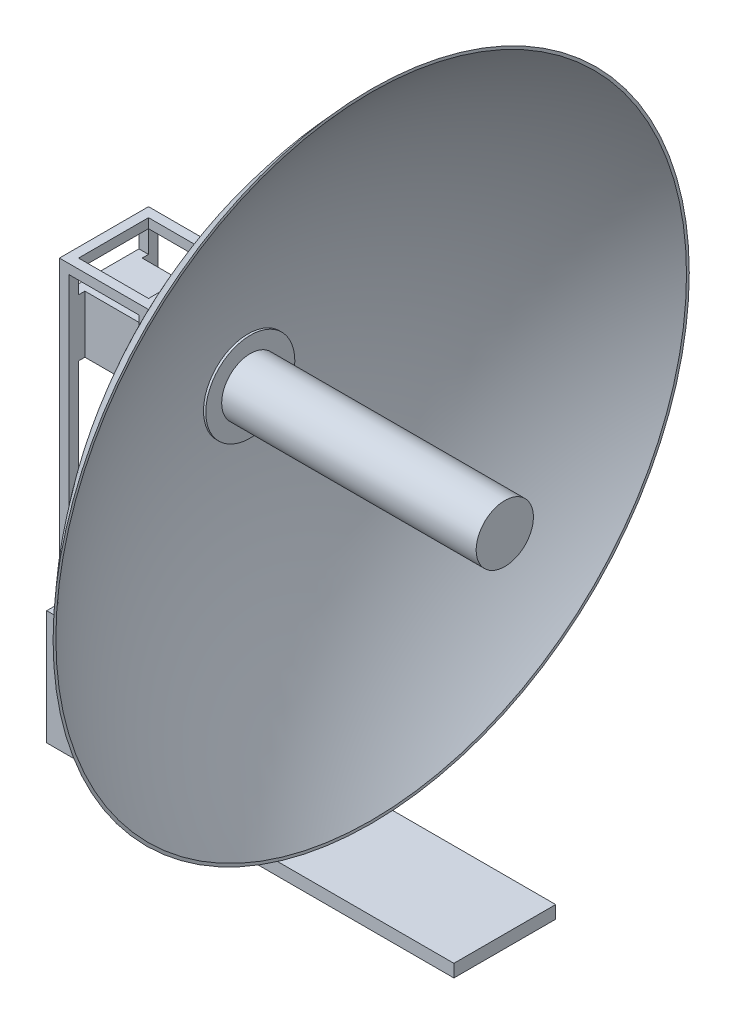
SolidWorks part; units mm, degrees
ref_plane "Front Plane" through (0, 0, 0) normal (0, 0, 1) x (1, 0, 0)
ref_plane "Top Plane" through (0, 0, 0) normal (0, 1, 0) x (1, 0, 0)
ref_plane "Right Plane" through (0, 0, 0) normal (1, 0, 0) x (0, 0, -1)
sketch "Sketch1" plane through (0, 0, 0) normal (0, 1, 0) x (1, 0, 0)
  line L1 (0, 0) -> (640, 0)
  line L2 (0, 0) -> (0, 160)
  line L3 (0, 160) -> (640, 160)
  line L4 (640, 0) -> (640, 160)
  dimension "D1" = 160
  dimension "D2" = 640
extrude "Boss-Extrude1" add sketch "Sketch1" along normal blind 180
sketch "Sketch2" plane through (640, 0, 0) normal (1, 0, 0) x (0, 0, -1)
  line L0 (160, 180) -> (160, 0) construction
  line L1 (0, 180) -> (160, 180)
  line L2 (0, 180) -> (0, 20)
  line L3 (0, 20) -> (160, 20)
  line L4 (160, 180) -> (160, 20)
  dimension "D1" = 160
extrude "Cut-Extrude1" cut sketch "Sketch2" against normal blind 480
sketch "Sketch3" plane through (160, 0, 0) normal (1, 0, 0) x (0, 0, -1)
  line L0 (0, 100) -> (160, 100) construction
  line L1 (0, 180) -> (0, 20) construction
  line L2 (160, 20) -> (160, 180) construction
  circle A0 centre (80, 100) radius 70
  dimension "D1" = 140
ref_plane "Plane1" through (0, 0, -80) normal (0, 0, 1) x (1, 0, 0)
ref_plane "Plane2" through (0, 100, 0) normal (0, 1, 0) x (1, 0, 0)
sketch "Sketch4" plane through (160, 0, 0) normal (1, 0, 0) x (0, 0, -1)
  line L0 (0, 180) -> (10, 180) construction
  line L1 (160, 180) -> (0, 180) construction
  line L2 (0, 180) -> (0, 170) construction
  line L3 (0, 180) -> (0, 20) construction
  line L4 (0, 170) -> (10, 170) construction
  line L5 (10, 170) -> (10, 180) construction
  line L6 (80, 180) -> (80, 20) construction
  line L7 (10, 170) -> (25, 170)
  line L8 (10, 170) -> (10, 155)
  line L9 (10, 155) -> (25, 155)
  line L10 (25, 170) -> (25, 155)
  line L11 (0, 20) -> (160, 20) construction
  line L12 (0, 100) -> (160, 100) construction
  line L13 (160, 20) -> (160, 180) construction
  line L14 (150, 155) -> (135, 155)
  line L15 (135, 170) -> (135, 155)
  line L16 (150, 170) -> (135, 170)
  line L17 (150, 170) -> (150, 155)
  line L18 (150, 30) -> (150, 45)
  line L19 (150, 30) -> (135, 30)
  line L20 (135, 30) -> (135, 45)
  line L21 (150, 45) -> (135, 45)
  line L22 (10, 45) -> (25, 45)
  line L23 (25, 30) -> (25, 45)
  line L24 (10, 30) -> (25, 30)
  line L25 (10, 30) -> (10, 45)
  dimension "D1" = 10
  dimension "D2" = 15
sketch "Sketch5" plane through (0, 180, 0) normal (0, 1, 0) x (1, 0, 0)
  line L0 (0, 160) -> (10, 160) construction
  line L1 (160, 160) -> (0, 160) construction
  line L2 (0, 160) -> (0, 150) construction
  line L3 (0, 160) -> (0, 0) construction
  line L4 (0, 150) -> (10, 150) construction
  line L5 (10, 150) -> (10, 160) construction
  line L6 (80, 160) -> (80, 0) construction
  line L7 (10, 150) -> (25, 150)
  line L8 (10, 150) -> (10, 135)
  line L9 (10, 135) -> (25, 135)
  line L10 (25, 150) -> (25, 135)
  line L11 (0, 0) -> (160, 0) construction
  line L12 (0, 80) -> (160, 80) construction
  line L13 (160, 0) -> (160, 160) construction
  line L14 (150, 135) -> (135, 135)
  line L15 (135, 150) -> (135, 135)
  line L16 (150, 150) -> (135, 150)
  line L17 (150, 150) -> (150, 135)
  line L18 (150, 10) -> (150, 25)
  line L19 (150, 10) -> (135, 10)
  line L20 (135, 10) -> (135, 25)
  line L21 (150, 25) -> (135, 25)
  line L22 (10, 25) -> (25, 25)
  line L23 (25, 10) -> (25, 25)
  line L24 (10, 10) -> (25, 10)
  line L25 (10, 10) -> (10, 25)
  dimension "D1" = 10
  dimension "D2" = 15
extrude "Boss-Extrude2" add sketch "Sketch5" along normal blind 480
sketch "Sketch6" plane through (25, 0, 0) normal (1, 0, 0) x (0, 0, -1)
  line L0 (25, 660) -> (25, 180) construction
  line L1 (10, 660) -> (25, 660)
  line L2 (10, 660) -> (10, 645)
  line L3 (10, 645) -> (25, 645)
  line L4 (25, 660) -> (25, 645)
  line L5 (150, 660) -> (150, 180) construction
  line L6 (135, 660) -> (150, 660)
  line L7 (135, 660) -> (135, 645)
  line L8 (135, 645) -> (150, 645)
  line L9 (150, 660) -> (150, 645)
  dimension "D1" = 15
extrude "Boss-Extrude3" add sketch "Sketch6" along normal up to surface (110 mm away) up to face at (135, 420, -17.5)
sketch "Sketch7" plane through (0, 0, -25) normal (0, 0, -1) x (-1, 0, 0)
  line L1 (-150, 660) -> (-135, 660)
  line L2 (-150, 660) -> (-150, 645)
  line L3 (-150, 645) -> (-135, 645)
  line L4 (-135, 660) -> (-135, 645)
  line L5 (-25, 645) -> (-10, 645)
  line L6 (-25, 645) -> (-25, 660)
  line L7 (-25, 660) -> (-10, 660)
  line L8 (-10, 645) -> (-10, 660)
extrude "Boss-Extrude4" add sketch "Sketch7" along normal up to surface (110 mm away) up to face at (80, 416.25, -135)
sketch "Sketch9" plane through (150, 0, 0) normal (1, 0, 0) x (0, 0, -1)
  line L0 (135, 645) -> (25, 645) construction
  line L2 (25, 645) -> (25, 180) construction
  line L3 (35, 520) -> (125, 520)
  line L4 (35, 520) -> (35, 610)
  line L5 (35, 610) -> (125, 610)
  line L6 (125, 520) -> (125, 610)
  line L7 (35, 520) -> (125, 610) construction
  line L8 (35, 610) -> (125, 520) construction
  point P4 (80, 565)
  dimension "D1" = 80
  dimension "D2" = 10
  dimension "D3" = 90
extrude "Boss-Extrude5" add sketch "Sketch9" against normal up to surface (140 mm away) separate body up to face at (10, 416.25, -80)
sketch "Sketch10" plane through (0, 0, -35) normal (0, 0, 1) x (1, 0, 0)
  line L0 (10, 520) -> (150, 520) construction
  line L1 (10, 610) -> (25, 610)
  line L2 (10, 610) -> (10, 520)
  line L3 (10, 520) -> (25, 520)
  line L4 (25, 610) -> (25, 520)
  line L5 (25, 645) -> (25, 180) construction
  line L6 (135, 645) -> (135, 180) construction
  line L7 (150, 610) -> (135, 610)
  line L8 (150, 610) -> (150, 520)
  line L9 (150, 520) -> (135, 520)
  line L10 (135, 610) -> (135, 520)
extrude "Boss-Extrude6" add sketch "Sketch10" along normal up to surface and the other way up to surface up to face at (17.5, 412.5, -25) other way up to face at (17.5, 412.5, -135)
sketch "Sketch8" plane through (150, 0, 0) normal (1, 0, 0) x (0, 0, -1)
  line L0 (80, 645) -> (80, 635) construction
  line L1 (135, 645) -> (25, 645) construction
  line L2 (80, 565) -> (80, 635) construction
  circle A0 centre (80, 565) radius 70
  dimension "D2" = 140
  dimension "D1" = 10
extrude "Boss-Extrude7" add sketch "Sketch8" along normal blind 80
sketch "Sketch11" plane through (0, 0, -80) normal (0, 0, 1) x (1, 0, 0)
  line L0 (150, 565) -> (640, 565) construction
  line L1 (640, 20) -> (640, 565) construction
  line L2 (230, 495) -> (230, 635) construction
  line L3 (430, 65) -> (430, 1065) construction
  line L4 (955, 1290) -> (955, -160)
  arc A0 (955, 1290) -> (955, -160) centre (955, 565) ccw
  point P13 (430, 565)
  dimension "D1" = 200
  dimension "D2" = 1000
revolve "Revolve1" add sketch "Sketch11" angle 360 about L4
sketch "Sketch12" plane through (0, 0, -80) normal (0, 0, 1) x (1, 0, 0)
  line L0 (230, 565) -> (430, 565) construction
  line L1 (230, 495) -> (230, 635) construction
  line L2 (430, -235) -> (430, 1365)
  line L3 (430, 1365) -> (2030, 1365)
  line L4 (2030, 1365) -> (2030, -235)
  line L5 (2030, -235) -> (430, -235)
  point P7 (430, 565)
  dimension "D1" = 200
  dimension "D2" = 1600
extrude "Cut-Extrude2" cut sketch "Sketch12" against normal through all both and the other way through all
shell "Shell1" thickness 3 removed face at (430, 65, -80)
sketch "Sketch13" plane through (230, 0, 0) normal (1, 0, 0) x (0, 0, -1)
  circle A1 centre (80, 565) radius 70
  circle A2 centre (80, 565) radius 70
  dimension "D1" = 0
extrude "Boss-Extrude8" add sketch "Sketch13" along normal blind 10
sketch "Sketch14" plane through (240, 0, 0) normal (1, 0, 0) x (0, 0, -1)
  circle A0 centre (80, 565) radius 45
  dimension "D1" = 90
extrude "Boss-Extrude9" add sketch "Sketch14" along normal up to surface (400 mm away) up to face at (640, 10, -80)
